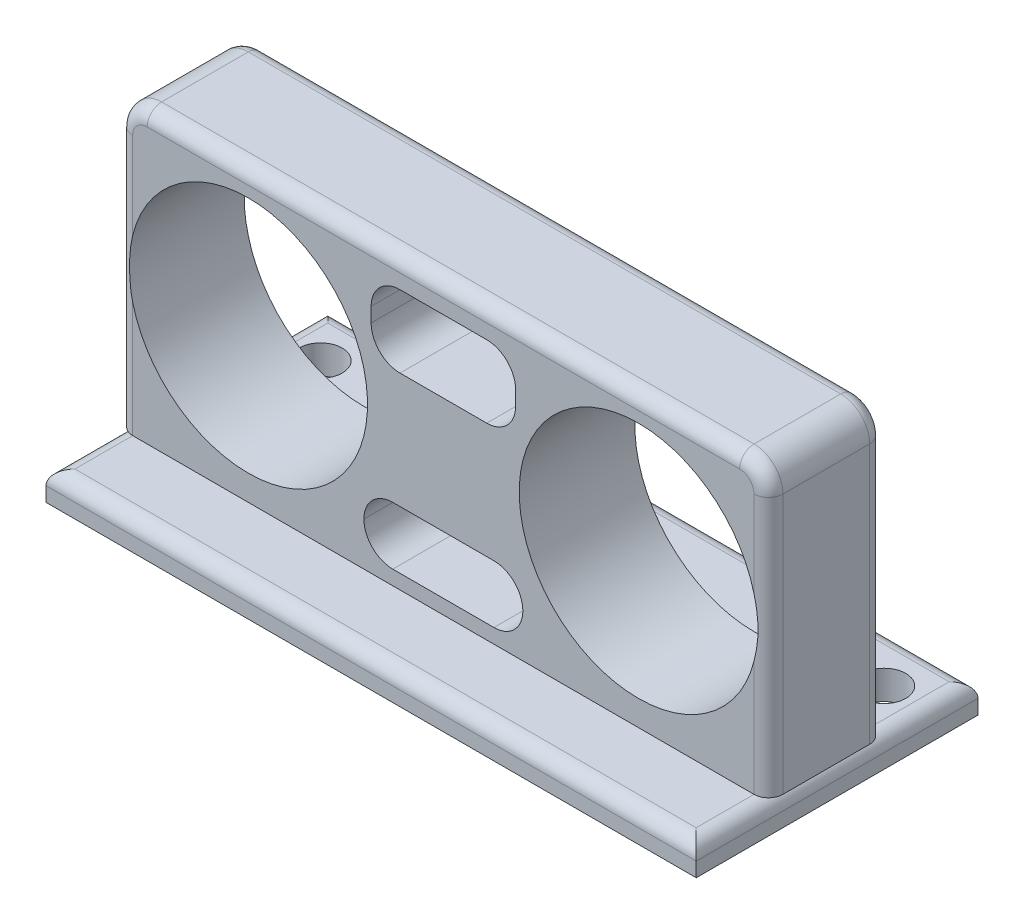
SolidWorks part; units mm, degrees
material "ABS"
ref_plane "Alzado" through (0, 0, 0) normal (0, 0, 1) x (1, 0, 0)
ref_plane "Planta" through (0, 0, 0) normal (0, 1, 0) x (1, 0, 0)
ref_plane "Vista lateral" through (0, 0, 0) normal (1, 0, 0) x (0, 0, -1)
sketch "Croquis1" plane through (0, 0, 0) normal (0, 0, 1) x (1, 0, 0)
  line L0 (0, -10) -> (9, -10) construction
  line L1 (0, 0) -> (45, 0)
  line L2 (0, 0) -> (0, -20)
  line L3 (0, -20) -> (45, -20)
  line L4 (45, 0) -> (45, -20)
  line L5 (45, -10) -> (36, -10) construction
  circle A0 centre (9, -10) radius 8.25
  circle A1 centre (36, -10) radius 8.25
  dimension "D4" = 16.5
  dimension "D6" = 16.5
  dimension "D1" = 45
  dimension "D2" = 20
  dimension "D3" = 9
  dimension "D5" = 9
extrude "Saliente-Extruir1" add sketch "Croquis1" along normal blind 8
sketch "Croquis2" plane through (0, -20, 0) normal (0, -1, 0) x (-1, 0, 0)
  line L0 (0, -2) -> (-45, -2) construction
  line L1 (0, -8) -> (0, 0) construction
  line L2 (-45, -8) -> (-45, 0) construction
  line L3 (0, 0) -> (-45, 0) construction
  line L5 (-45, -13) -> (0, -13)
  line L6 (-45, -13) -> (-45, 10)
  line L7 (-45, 10) -> (0, 10)
  line L8 (0, -13) -> (0, 10)
  line L9 (0, -8) -> (-45, -8) construction
  line L10 (0, -6) -> (-45, -6) construction
  dimension "D1" = 2
  dimension "D2" = 12
  dimension "D3" = 2
  dimension "D4" = 7
  dimension "D5" = 45
extrude "Saliente-Extruir2" add sketch "Croquis2" along normal blind 2 separate body
sketch "Croquis4" plane through (0, 0, 0) normal (0, 0, -1) x (-1, 0, 0)
  line L0 (-22.5, 0) -> (-22.5, -20) construction
  line L1 (-45, 0) -> (0, 0) construction
  line L2 (0, -20) -> (-45, -20) construction
  line L3 (-45, 0) -> (0, 0) construction
  line L4 (-28, -15) -> (-17, -15)
  line L5 (-28, -15) -> (-28, -19)
  line L6 (-28, -19) -> (-17, -19)
  line L7 (-17, -15) -> (-17, -19)
  line L9 (-17.5, -7) -> (-17.5, -2)
  line L10 (-27.5, -2) -> (-17.5, -2)
  line L11 (-27.5, -7) -> (-27.5, -2)
  line L12 (-27.5, -7) -> (-17.5, -7)
  dimension "D1" = 11
  dimension "D2" = 5.5
  dimension "D3" = 4
  dimension "D4" = 15
  dimension "D5" = 2
  dimension "D6" = 5
  dimension "D7" = 10
  dimension "D8" = 5
  dimension "D9" = 90
  dimension "D10" = 90
extrude "Cortar-Extruir3" cut sketch "Croquis4" against normal through all
sketch "Croquis5" plane through (0, -20, 0) normal (0, 1, 0) x (1, 0, 0)
  line L0 (0, 10) -> (45, 10) construction
  line L1 (0, -13) -> (0, 10) construction
  line L2 (45, 10) -> (45, -13) construction
  circle A0 centre (3, 3) radius 1.5
  circle A1 centre (42, 3) radius 1.5
  dimension "D1" = 3
  dimension "D2" = 7
  dimension "D4" = 3
  dimension "D5" = 7
  dimension "D6" = 3
  dimension "D3" = 3
extrude "Cortar-Extruir4" cut sketch "Croquis5" against normal through all
fillet "Redondeo1" radius 2 4 edges at (17, -19, 4) (28, -15, 4) (17, -15, 4) (28, -19, 4)
fillet "Redondeo2" radius 2 6 edges at (45, 0, 4) (0, 0, 4) (27.5, -7, 4) (27.5, -2, 4) (17.5, -2, 4) (17.5, -7, 4)
fillet "Redondeo3" radius 1 10 edges at (45, -11, 8) (44.4142, -0.5858, 8) (0, -11, 8) (0.5858, -0.5858, 8) (45, -11, 0) (44.4142, -0.5858, 0) (0, -11, 0) (0.5858, -0.5858, 0) (22.5, 0, 8) (22.5, 0, 0)
sketch "Croquis6" plane through (0, -20, 0) normal (0, 1, 0) x (1, 0, 0)
  line L0 (45, 10) -> (45, -13) construction
  line L1 (0, 10) -> (45, 10)
  line L2 (0, 10) -> (0, 6.5)
  line L3 (0, 6.5) -> (45, 6.5)
  line L4 (45, 10) -> (45, 6.5)
  dimension "D1" = 3.5
extrude "Cortar-Extruir5" cut sketch "Croquis6" against normal through all
fillet "Redondeo4" radius 1 4 edges at (45, -20, 3.25) (22.5, -20, 13) (22.5, -20, -6.5) (0, -20, 3.25)
